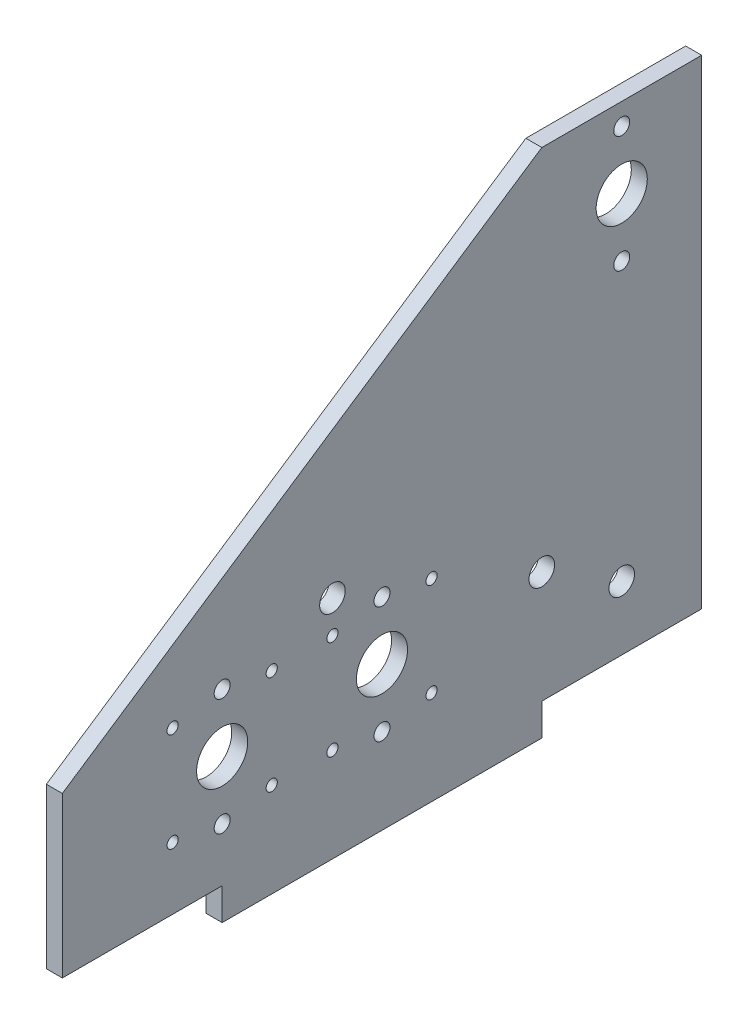
SolidWorks part; units mm, degrees
ref_plane "Alzado" through (0, 0, 0) normal (0, 0, 1) x (1, 0, 0)
ref_plane "Planta" through (0, 0, 0) normal (0, 1, 0) x (1, 0, 0)
ref_plane "Vista lateral" through (0, 0, 0) normal (1, 0, 0) x (0, 0, -1)
sketch "Croquis1" plane through (0, 0, 0) normal (1, 0, 0) x (0, 0, -1)
  line L0 (150, 150) -> (0, 50)
  line L1 (0, 0) -> (50, 0)
  line L2 (0, 0) -> (0, 50)
  line L3 (150, 150) -> (200, 150)
  line L4 (200, 0) -> (200, 150)
  line L5 (200, 75) -> (37.5, 75) construction
  line L6 (175, 150) -> (175, 0) construction
  line L7 (100, 116.6667) -> (100, -10) construction
  line L8 (84.5, 106.3333) -> (84.5, -10) construction
  line L9 (50, 0) -> (50, -10)
  line L10 (50, -10) -> (150, -10)
  line L11 (150, 0) -> (150, -10)
  line L12 (154, 35) -> (0, 35) construction
  line L14 (150, 0) -> (200, 0)
  circle A0 centre (175, 125) radius 8
  circle A1 centre (175, 20) radius 4
  circle A2 centre (150, 35) radius 4
  circle A3 centre (175, 143.25) radius 2.5
  circle A4 centre (175, 106.75) radius 2.5
  circle A5 centre (100, 35) radius 8
  circle A6 centre (84.5, 60.6856) radius 4
  circle A7 centre (100, 53.25) radius 2.5
  circle A8 centre (100, 16.75) radius 2.5
  circle A9 centre (84.5, 50.5) radius 1.75
  circle A10 centre (115.5, 50.5) radius 1.75
  circle A11 centre (115.5, 19.5) radius 1.75
  circle A12 centre (84.5, 19.5) radius 1.75
  circle A13 centre (50, 35) radius 8
  circle A14 centre (50, 53.25) radius 2.5
  circle A15 centre (50, 16.75) radius 2.5
  circle A16 centre (34.5, 50.5) radius 1.75
  circle A17 centre (65.5, 50.5) radius 1.75
  circle A18 centre (65.5, 19.5) radius 1.75
  circle A19 centre (34.5, 19.5) radius 1.75
  dimension "D6" = 16
  dimension "D10" = 8
  dimension "D12" = 8
  dimension "D15" = 5
  dimension "D16" = 5
  dimension "D20" = 45
  dimension "D22" = 2
  dimension "D23" = 18.25
  dimension "D24" = 5
  dimension "D27" = 3.5
  dimension "D21" = 8
  dimension "D1" = 150
  dimension "D2" = 200
  dimension "D3" = 50
  dimension "D4" = 50
  dimension "D5" = 50
  dimension "D7" = 100
  dimension "D8" = 50
  dimension "D9" = 10
  dimension "D11" = 20
  dimension "D13" = 25
  dimension "D14" = 15
  dimension "D17" = 18.25
  dimension "D18" = 18.25
  dimension "D19" = 30
  dimension "D25" = 2
  dimension "D26" = 15.5
  dimension "D28" = 15.5
  dimension "D29" = 2
  dimension "D30" = 2
extrude "Saliente-Extruir1" add sketch "Croquis1" along normal blind 5
